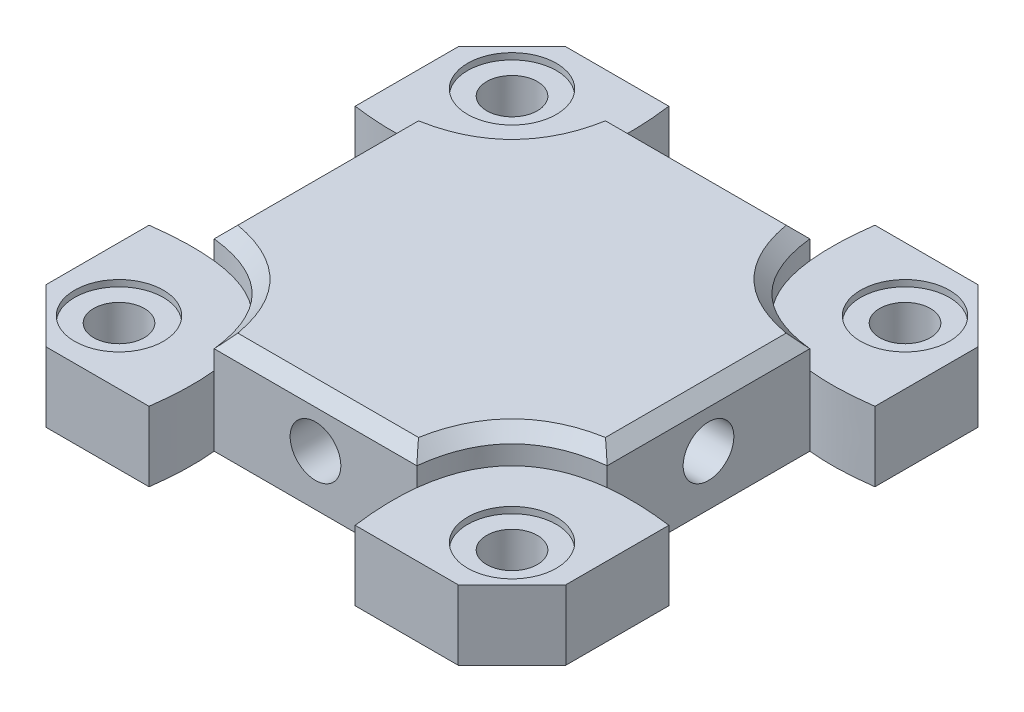
SolidWorks part; units mm, degrees
ref_plane "Front Plane" through (0, 0, 0) normal (0, 0, 1) x (1, 0, 0)
ref_plane "Top Plane" through (0, 0, 0) normal (0, 1, 0) x (1, 0, 0)
ref_plane "Right Plane" through (0, 0, 0) normal (1, 0, 0) x (0, 0, -1)
sketch "Sketch2" plane through (0, 0, 0) normal (0, 1, 0) x (1, 0, 0)
  line L1 (-20.5, -20.5) -> (20.5, -20.5)
  line L2 (-20.5, -20.5) -> (-20.5, 20.5)
  line L3 (-20.5, 20.5) -> (20.5, 20.5)
  line L4 (20.5, -20.5) -> (20.5, 20.5)
  line L5 (-20.5, -20.5) -> (20.5, 20.5) construction
  line L6 (-20.5, 20.5) -> (20.5, -20.5) construction
  point P0 (0, 0)
  dimension "D1" = 41
  dimension "D2" = 41
extrude "Boss-Extrude1" add sketch "Sketch2" along normal blind 2
sketch "Sketch3" plane through (0, 0, 0) normal (0, -1, 0) x (1, 0, 0)
  line L0 (-7.9432, -8.0372) -> (0, 0) construction
  line L5 (-7.9432, -8.0372) -> (7.9432, -8.0372) construction
  line L6 (-7.9432, -8.0372) -> (-7.9432, 8.0372) construction
  line L7 (-7.9432, 8.0372) -> (7.9432, 8.0372) construction
  line L8 (7.9432, -8.0372) -> (7.9432, 8.0372) construction
  line L9 (0, 0) -> (7.9432, 8.0372) construction
  line L10 (0, 0) -> (7.9432, -8.0372) construction
  line L11 (-7.9432, 8.0372) -> (0, 0) construction
  arc A1 (7.9432, 8.0372) -> (-7.9432, 8.0372) centre (0, 0) ccw construction
  arc A2 (-7.9432, -8.0372) -> (7.9432, -8.0372) centre (0, 0) ccw construction
  arc A3 (-7.9432, 8.0372) -> (-7.9432, -8.0372) centre (0, 0) ccw construction
  arc A4 (7.9432, -8.0372) -> (8.0686, 7.9112) centre (0, 0) ccw construction
  circle A5 centre (-7.9432, 8.0372) radius 2
  circle A10 centre (8.0372, 7.9432) radius 2
  circle A12 centre (7.9432, -8.0372) radius 2
  circle A13 centre (-8.0372, -7.9432) radius 2
  arc A14 (8.0686, 7.9112) -> (7.9432, 8.0372) centre (0, 0) ccw construction
  point P15 (-1.4144, -0.0142)
  point P19 (0, 0)
  dimension "D1" = 22.6
  dimension "D2" = 4
  dimension "D4" = 4
extrude "Cut-Extrude1" cut sketch "Sketch3" against normal through all
sketch "Sketch4" plane through (0, 2, 0) normal (0, 1, 0) x (1, 0, 0)
  circle A0 centre (0, 0) radius 7.5
  dimension "D1" = 15
extrude "Cut-Extrude2" cut sketch "Sketch4" against normal through all
sketch "Sketch5" plane through (0, 0, 0) normal (0, -1, 0) x (1, 0, 0)
  line L1 (-12.5, -12.5) -> (12.5, -12.5)
  line L2 (-12.5, -12.5) -> (-12.5, 12.5)
  line L3 (-12.5, 12.5) -> (12.5, 12.5)
  line L4 (12.5, -12.5) -> (12.5, 12.5)
  line L5 (-12.5, -12.5) -> (12.5, 12.5) construction
  line L6 (-12.5, 12.5) -> (12.5, -12.5) construction
  point P0 (0, 0)
  dimension "D1" = 25
  dimension "D2" = 25
extrude "Cut-Extrude3" cut sketch "Sketch5" against normal blind 1
sketch "Sketch6" plane through (0, 2, 0) normal (0, 1, 0) x (1, 0, 0)
  line L0 (-20.5, 16.2574) -> (-16.2574, 20.5)
  line L1 (-20.5, 20.5) -> (-20.5, -20.5) construction
  line L2 (20.5, 20.5) -> (-20.5, 20.5) construction
  line L4 (16.2574, 20.5) -> (20.5, 16.2574)
  line L5 (20.5, -20.5) -> (20.5, 20.5) construction
  line L7 (20.5, -16.2574) -> (16.2574, -20.5)
  line L8 (-20.5, -20.5) -> (20.5, -20.5) construction
  line L10 (-16.2574, -20.5) -> (-20.5, -16.2574)
  line L12 (-2.4898, 0) -> (5.6129, 0) construction
  line L13 (0, 5.0948) -> (0, 0) construction
  line L14 (0, 0) -> (3.8649, 3.8649) construction
  line L15 (-20.5, -16.2574) -> (-20.5, -20.5)
  line L16 (-20.5, -20.5) -> (-16.2574, -20.5)
  line L17 (16.2574, -20.5) -> (20.5, -20.5)
  line L18 (20.5, -20.5) -> (20.5, -16.2574)
  line L19 (20.5, 16.2574) -> (20.5, 20.5)
  line L20 (20.5, 20.5) -> (16.2574, 20.5)
  line L21 (-16.2574, 20.5) -> (-20.5, 20.5)
  line L22 (-20.5, 20.5) -> (-20.5, 16.2574)
  dimension "D1" = 6
  dimension "D2" = 6
  dimension "D3" = 45
  dimension "D4" = 6
  dimension "D5" = 6
extrude "Cut-Extrude4" cut sketch "Sketch6" against normal through all
sketch "Sketch7" plane through (0, 0, 0) normal (0, -1, 0) x (1, 0, 0)
  line L0 (-15.5, 15.5) -> (0, 0) construction
  line L1 (-15.5, -15.5) -> (15.5, -15.5) construction
  line L2 (-15.5, -15.5) -> (-15.5, 15.5) construction
  line L3 (-15.5, 15.5) -> (15.5, 15.5) construction
  line L4 (15.5, -15.5) -> (15.5, 15.5) construction
  line L5 (-15.5, -15.5) -> (0, 0) construction
  line L6 (0, 0) -> (15.5, -15.5) construction
  line L7 (0, 0) -> (15.5, 15.5) construction
  arc A0 (-15.5, -15.5) -> (15.5, -15.5) centre (0, 0) ccw construction
  arc A1 (-15.5, 15.5) -> (-15.5, -15.5) centre (0, 0) ccw construction
  arc A2 (15.5, -15.5) -> (15.5, 15.5) centre (0, 0) ccw construction
  arc A3 (15.5, 15.5) -> (-15.5, 15.5) centre (0, 0) ccw construction
  circle A4 centre (-15.5, 15.5) radius 2
  circle A5 centre (15.5, 15.5) radius 2
  circle A6 centre (15.5, -15.5) radius 2
  circle A7 centre (-15.5, -15.5) radius 2
  point P16 (0, 0)
  dimension "D2" = 4
  dimension "D4" = 31
  dimension "D3" = 4
extrude "Cut-Extrude5" cut sketch "Sketch7" against normal through all
sketch "Sketch8" plane through (0, 0, 0) normal (0, -1, 0) x (1, 0, 0)
  line L0 (-12.5, -12.5) -> (-12.5, 12.5) construction
  line L1 (-12.5, -12.5) -> (-20.477, -12.5) construction
  line L2 (-12.5, 12.5) -> (-20.477, 12.5) construction
  line L3 (-20.477, -12.5) -> (-20.477, 12.5) construction
  line L4 (12.5, -12.5) -> (12.5, 12.5) construction
  line L5 (12.5, -12.5) -> (20.4876, -12.5) construction
  line L6 (12.5, 12.5) -> (20.4876, 12.5) construction
  line L7 (20.4876, -12.5) -> (20.4876, 12.5) construction
  line L8 (-12.5, 12.5) -> (12.5, 12.5)
  line L9 (-12.5, 12.5) -> (-12.5, 20.5)
  line L10 (12.5, 12.5) -> (12.5, 20.5)
  line L11 (-12.5, 20.5) -> (12.5, 20.5)
  line L12 (12.5, -12.5) -> (-12.5, -12.5)
  line L13 (12.5, -12.5) -> (12.5, -20.4578)
  line L14 (-12.5, -12.5) -> (-12.5, -20.4578)
  line L15 (12.5, -20.4578) -> (-12.5, -20.4578)
  line L16 (-16.2574, 20.5) -> (16.2574, 20.5) construction
extrude "Boss-Extrude2" add sketch "Sketch8" along normal blind 3.5
sketch "Sketch9" plane through (0, -3.5, 0) normal (0, -1, 0) x (1, 0, 0)
  circle A0 centre (0, 16.5) radius 2
  circle A1 centre (0, -16.4789) radius 2
  dimension "D1" = 4
extrude "Cut-Extrude6" cut sketch "Sketch9" against normal through all
sketch "Sketch10" plane through (0, 0, 0) normal (0, -1, 0) x (1, 0, 0)
  line L0 (-20.5, -16.2574) -> (-16.2574, -20.5)
  line L1 (20.5, 12.5) -> (12.5, 12.5)
  line L2 (20.5, 12.5) -> (20.5, 16.2574)
  line L3 (16.2574, 20.5) -> (12.5, 20.5)
  line L4 (-20.5, 12.5) -> (-20.5, 16.2574)
  line L5 (-20.5, -12.5) -> (-12.5, -12.5)
  line L6 (-20.5, -12.5) -> (-20.5, -16.2574)
  line L8 (20.5, -12.5) -> (20.5, -16.2574)
  line L9 (-20.5, 16.2574) -> (-16.2574, 20.5)
  line L10 (16.2574, 20.5) -> (20.5, 16.2574)
  line L11 (20.5, -16.2574) -> (16.2574, -20.5)
  line L12 (-20.5, -12.5) -> (-20.5, -16.2574)
  line L13 (-12.5, 12.5) -> (-20.5, 12.5)
  line L14 (-12.5, 20.5) -> (-16.2574, 20.5)
  line L15 (12.5, -12.5) -> (20.5, -12.5)
  line L16 (-12.5, -12.5) -> (-12.5, 12.5)
  line L17 (-12.5, 12.5) -> (-12.5, 20.5)
  line L18 (-12.5, 20.5) -> (-16.2574, 20.5)
  line L19 (-16.2574, 20.5) -> (-20.5, 16.2574)
  line L20 (-20.5, 16.2574) -> (-20.5, -16.2574)
  line L21 (-20.5, -16.2574) -> (-16.2574, -20.5)
  line L22 (-16.2574, -20.5) -> (16.2574, -20.5)
  line L23 (16.2574, -20.5) -> (20.5, -16.2574)
  line L24 (20.5, -16.2574) -> (20.5, 16.2574)
  line L25 (20.5, 16.2574) -> (16.2574, 20.5)
  line L26 (16.2574, 20.5) -> (12.5, 20.5)
  line L27 (12.5, 20.5) -> (12.5, 12.5)
  line L28 (12.5, 12.5) -> (12.5, -12.5)
  line L29 (12.5, -12.5) -> (12.5, -20.4578)
  line L30 (12.5, -20.4578) -> (-12.5, -20.4578)
  line L31 (-12.5, -20.4578) -> (-12.5, -12.5)
  line L33 (-12.5, 12.5) -> (-12.5, 20.5)
  line L34 (-12.5, 20.5) -> (-16.2574, 20.5)
  line L35 (-16.2574, 20.5) -> (-20.5, 16.2574)
  line L36 (-20.5, 16.2574) -> (-20.5, 12.5)
  line L37 (-20.5, -16.2574) -> (-16.2574, -20.5)
  line L39 (16.2574, -20.5) -> (20.5, -16.2574)
  line L40 (20.5, -16.2574) -> (20.5, 16.2574)
  line L41 (20.5, 16.2574) -> (16.2574, 20.5)
  line L42 (16.2574, 20.5) -> (12.5, 20.5)
  line L43 (12.5, 20.5) -> (12.5, 12.5)
  line L44 (12.5, 12.5) -> (12.5, -12.5)
  line L45 (12.5, -12.5) -> (12.5, -20.4578)
  line L47 (-12.5, -20.4578) -> (-12.5, -12.5)
  line L50 (12.5, 20.5) -> (-12.5, 20.5) construction
  circle A0 centre (-15.5, 15.5) radius 2
  circle A1 centre (15.5, 15.5) radius 2
  circle A2 centre (15.5, -15.5) radius 2
  circle A3 centre (-15.5, -15.5) radius 2
  circle M19 centre (-15.5, -15.5) radius 2
  circle M20 centre (15.5, -15.5) radius 2
  circle M21 centre (15.5, 15.5) radius 2
  circle M22 centre (-15.5, 15.5) radius 2
  line M24 (-12.5, 12.5) -> (-12.5, 20.5)
  line M25 (-12.5, 20.5) -> (-16.2574, 20.5)
  line M26 (-16.2574, 20.5) -> (-20.5, 16.2574)
  line M27 (-20.5, 16.2574) -> (-20.5, -16.2574)
  line M28 (-20.5, -16.2574) -> (-16.2574, -20.5)
  line M29 (-16.2574, -20.5) -> (16.2574, -20.5)
  line M30 (16.2574, -20.5) -> (20.5, -16.2574)
  line M31 (20.5, -16.2574) -> (20.5, 16.2574)
  line M32 (20.5, 16.2574) -> (16.2574, 20.5)
  line M33 (16.2574, 20.5) -> (12.5, 20.5)
  line M34 (12.5, 20.5) -> (12.5, 12.5)
  line M36 (12.5, -12.5) -> (12.5, -20.4578)
  line M37 (12.5, -20.4578) -> (-12.5, -20.4578)
  line M38 (-12.5, -20.4578) -> (-12.5, -12.5)
  dimension "D1" = 0
extrude "Boss-Extrude3" add sketch "Sketch10" along normal up to surface (3.5 mm away) contours L13 M24 M25 M26 M27 M22 | L1 M31 M32 M33 M34 M21 | L15 L5 M36 M37 M38 M27 M28 M29 M30 M31 M19 M20 region at (-20.0823, 0, -14.3787) region at (-20.3869, 0, 14.3787) region at (16.5, 0, 12.6131) up to face at (0, -3.5, 14.5)
sketch "Sketch11" plane through (0, 2, 0) normal (0, 1, 0) x (1, 0, 0)
  circle A0 centre (-15.5, 15.5) radius 3.5
  circle A1 centre (15.5, 15.5) radius 3.5
  circle A2 centre (15.5, -15.5) radius 3.5
  circle A3 centre (-15.5, -15.5) radius 3.5
  point P12 (0, 0)
  dimension "D1" = 7
  dimension "D2" = 4
extrude "Cut-Extrude7" cut sketch "Sketch11" against normal offset from surface (3.5 mm away) 2 up to face at (0, -3.5, -18.4789)
sketch "Sketch12" plane through (0, 0, 0) normal (0, -1, 0) x (1, 0, 0)
  line L0 (-12.5, 12.5) -> (-12.5, -12.5) construction
  line L1 (-20.5, -12.5) -> (-12.5, -12.5)
  line L2 (-20.5, -12.5) -> (-20.5, -10.5)
  line L3 (-20.5, -10.5) -> (-12.5, -10.5)
  line L4 (-12.5, -12.5) -> (-12.5, -10.5)
  line L5 (-25.9518, 0) -> (26.3784, 0) construction
  line L6 (0, 23.4974) -> (0, -23.7021) construction
  line L7 (-12.5, 12.5) -> (-12.5, 10.5)
  line L8 (-20.5, 12.5) -> (-12.5, 12.5)
  line L9 (-20.5, 12.5) -> (-20.5, 10.5)
  line L10 (-20.5, 10.5) -> (-12.5, 10.5)
  line L11 (12.5, -12.5) -> (12.5, -10.5)
  line L12 (20.5, -10.5) -> (12.5, -10.5)
  line L13 (20.5, -12.5) -> (20.5, -10.5)
  line L14 (20.5, -12.5) -> (12.5, -12.5)
  line L15 (20.5, 10.5) -> (12.5, 10.5)
  line L16 (20.5, 12.5) -> (20.5, 10.5)
  line L17 (20.5, 12.5) -> (12.5, 12.5)
  line L18 (12.5, 12.5) -> (12.5, 10.5)
  dimension "D1" = 2
extrude "Boss-Extrude4" add sketch "Sketch12" along normal up to surface (3.5 mm away) up to face at (0, -3.5, 14.5)
sketch "Sketch13" plane through (0, 2, 0) normal (0, 1, 0) x (1, 0, 0)
  circle A0 centre (-15.5, 15.5) radius 3.5
  circle A1 centre (15.5, 15.5) radius 3.5
  circle A2 centre (15.5, -15.5) radius 3.5
  circle A3 centre (-15.5, -15.5) radius 3.5
  point P12 (0, 0)
  dimension "D1" = 4
extrude "Cut-Extrude8" cut sketch "Sketch13" against normal up to surface (3.5 mm away) up to face at (-15.5, -1.5, -13.5)
sketch "Sketch14" plane through (0, -1.5, 0) normal (0, 1, 0) x (1, 0, 0)
  circle A0 centre (-15.5, -15.5) radius 2
  circle A1 centre (-15.5, -15.5) radius 3.5
  circle A2 centre (-15.5, 15.5) radius 3.5
  circle A3 centre (-15.5, 15.5) radius 2
  circle A4 centre (15.5, 15.5) radius 3.5
  circle A5 centre (15.5, 15.5) radius 2
  circle A6 centre (15.5, -15.5) radius 3.5
  circle A7 centre (15.5, -15.5) radius 2
  point P16 (0, 0)
  dimension "D1" = 4
extrude "Boss-Extrude5" add sketch "Sketch14" along normal offset from surface (3 mm away) 0.5 up to face at (-15.5, 2, 19)
sketch "Sketch15" plane through (0, 2, 0) normal (0, 1, 0) x (1, 0, 0)
  line L0 (0, 20.5) -> (0, -20.5) construction
  line L1 (16.2574, 20.5) -> (-16.2574, 20.5) construction
  line L2 (-16.2574, -20.5) -> (16.2574, -20.5) construction
  line L3 (0, -16.5) -> (8, -16.5) construction
  line L4 (0, -16.5) -> (-8, -16.5) construction
  line L5 (0, 16.4789) -> (8, 16.4789) construction
  line L6 (0, 16.4789) -> (-8, 16.4789) construction
  line L7 (-8, 20.5) -> (-8, 16.4789) construction
  line L8 (-8, 16.4789) -> (-8, 12.4578) construction
  line L9 (-8, -20.5) -> (-8, -16.5) construction
  line L10 (-8, -16.5) -> (-8, -12.5) construction
  line L11 (-3.025, 0) -> (3.025, 0) construction
  line L12 (8, 12.4578) -> (-8, 12.4578)
  line L13 (8, 12.4578) -> (8, 20.5)
  line L14 (8, 20.5) -> (-8, 20.5)
  line L15 (-8, 12.4578) -> (-8, 20.5)
  line L16 (8, -12.5) -> (-8, -12.5)
  line L17 (8, -12.5) -> (8, -20.5)
  line L18 (8, -20.5) -> (-8, -20.5)
  line L19 (-8, -12.5) -> (-8, -20.5)
  circle A0 centre (0, 16.4789) radius 2
  circle A1 centre (0, -16.4789) radius 2
  dimension "D1" = 8
extrude "Boss-Extrude6" add sketch "Sketch15" along normal blind 4
chamfer "Chamfer1" distance 0.5 angle 45 2 edges at (0, 6, 14.4789) (0, 6, -14.4789)
chamfer "Chamfer2" distance 0.5 angle 45 8 edges at (8, 6, 16.5) (0, 6, 20.5) (-8, 6, 16.5) (0, 6, 12.5) (-8, 6, -16.4789) (0, 6, -20.5) (8, 6, -16.4789) (0, 6, -12.4578)
sketch "Sketch16" plane through (0, -3.5, 0) normal (0, -1, 0) x (1, 0, 0)
  line L0 (-20.5, 10.5) -> (-20.5, 16.2574) construction
  line L1 (-12.5, -12.5) -> (-20.5, -12.5)
  line L2 (-12.5, -12.5) -> (-12.5, 12.5)
  line L3 (-12.5, 12.5) -> (-20.5, 12.5)
  line L4 (-20.5, -12.5) -> (-20.5, 12.5)
  line L5 (12.5, 12.5) -> (20.5, 12.5)
  line L6 (12.5, 12.5) -> (12.5, -12.5)
  line L7 (20.5, 12.5) -> (20.5, -12.5)
  line L8 (12.5, -12.5) -> (20.5, -12.5)
  line L9 (20.5, 16.2574) -> (20.5, 10.5) construction
extrude "Cut-Extrude9" cut sketch "Sketch16" against normal up to surface (3.5 mm away) up to face at (16.5, 0, 0)
sketch "Sketch17" plane through (0, 6, 0) normal (0, 1, 0) x (1, 0, 0)
  line L1 (15.3001, -24.9451) -> (-15.3001, -24.9451)
  line L2 (15.3001, -24.9451) -> (15.3001, 24.9451)
  line L3 (15.3001, 24.9451) -> (-15.3001, 24.9451)
  line L4 (-15.3001, -24.9451) -> (-15.3001, 24.9451)
  line L5 (15.3001, -24.9451) -> (-15.3001, 24.9451) construction
  line L6 (15.3001, 24.9451) -> (-15.3001, -24.9451) construction
  point P0 (0, 0)
extrude "Cut-Extrude10" cut sketch "Sketch17" against normal up to surface (4 mm away) up to face at (0, 2, 0.0053)
sketch "Sketch18" plane through (0, 2, 0) normal (0, 1, 0) x (1, 0, 0)
  circle A0 centre (0, 0) radius 14.015
extrude "Boss-Extrude7" add sketch "Sketch18" against normal up to surface (1 mm away) up to face at (8.0372, 1, 9.9432)
sketch "Sketch19" plane through (0, 2, 0) normal (0, 1, 0) x (1, 0, 0)
  circle A0 centre (0, 16.4789) radius 2
  circle A1 centre (0, -16.5) radius 2
extrude "Boss-Extrude8" add sketch "Sketch19" against normal up to surface (5.5 mm away) up to face at (0, -3.5, -18.4789)
sketch "Sketch20" plane through (0, 2, 0) normal (0, 1, 0) x (1, 0, 0)
  line L0 (0, 0) -> (-10, 0) construction
  circle A0 centre (-10, 0) radius 2
  circle A1 centre (0, 10) radius 2
  circle A2 centre (10, 0) radius 2
  circle A3 centre (0, -10) radius 2
  point P13 (0, 0)
  dimension "D2" = 4
  dimension "D1" = 10
  dimension "D3" = 4
sketch "Sketch21" plane through (0, 1, 0) normal (0, -1, 0) x (1, 0, 0)
  line L0 (-20.5, -16.2574) -> (-20.5, -12.5) construction
  line L1 (20.5, 12.5) -> (-20.5, 12.5)
  line L2 (20.5, 12.5) -> (20.5, -12.5)
  line L3 (20.5, -12.5) -> (-20.5, -12.5)
  line L4 (-20.5, 12.5) -> (-20.5, -12.5)
  line L5 (20.5, 12.5) -> (-20.5, -12.5) construction
  line L6 (20.5, -12.5) -> (-20.5, 12.5) construction
  line L7 (20.5, -12.5) -> (-20.5, -12.5) construction
  point P0 (0, 0)
extrude "Boss-Extrude9" add sketch "Sketch21" along normal up to surface (4.5 mm away) up to face at (0, -3.5, -16.4191)
sketch "Sketch22" plane through (0, 2, 0) normal (0, 1, 0) x (1, 0, 0)
  line L0 (0, 20.5) -> (0, 0) construction
  line L1 (16.2574, 20.5) -> (-16.2574, 20.5) construction
  line L2 (0, 0) -> (-20.5, 0) construction
  line L3 (-20.5, 16.2574) -> (-20.5, -16.2574) construction
  line L4 (0, 0) -> (0, -20.5) construction
  line L5 (-16.2574, -20.5) -> (16.2574, -20.5) construction
  line L6 (0, 0) -> (20.5, 0) construction
  line L7 (20.5, -16.2574) -> (20.5, 16.2574) construction
  line L8 (-20.5, 0) -> (-20.5, 16.2574) construction
  line L9 (0, 20.5) -> (-16.2574, 20.5) construction
  line L10 (-20.5, 0) -> (-20.5, -16.2574) construction
  line L11 (0, -20.5) -> (-16.2574, -20.5) construction
  line L12 (-8.1287, -20.5) -> (-20.5, -8.1287) construction
  line L13 (-8.1287, 20.5) -> (-20.5, 8.1287) construction
  line L14 (0, -20.5) -> (16.2574, -20.5) construction
  line L15 (20.5, 0) -> (20.5, -16.2574) construction
  line L16 (8.1287, -20.5) -> (20.5, -8.1287) construction
  line L17 (0, 20.5) -> (16.2574, 20.5) construction
  line L18 (20.5, 16.2574) -> (20.5, 0) construction
  line L19 (20.5, 8.1287) -> (8.1287, 20.5) construction
  line L20 (-14.3143, 14.3143) -> (-10.25, 10.25) construction
  line L21 (-10.25, -10.25) -> (-14.3143, -14.3143) construction
  line L22 (-20.5, 0) -> (0, 20.5) construction
  line L23 (0, 20.5) -> (20.5, 0) construction
  line L24 (20.5, 0) -> (0, -20.5) construction
  line L25 (0, -20.5) -> (-20.5, 0) construction
  line L26 (10.25, 10.25) -> (14.3143, 14.3143) construction
  line L27 (10.25, -10.25) -> (14.3143, -14.3143) construction
  line L28 (-20.5, 8.1287) -> (-20.5, -8.1287)
  line L29 (-8.1287, -20.5) -> (8.1287, -20.5)
  line L30 (20.5, -8.1287) -> (20.5, 8.1287)
  line L31 (-8.1287, 20.5) -> (8.1287, 20.5)
  spline S0 degree 2 poles (-8.1287, 20.5) (-6.1857, 6.1857) (-20.5, 8.1287) knots 0 0 0 1 1 1
  spline S1 degree 2 poles (8.1287, -20.5) (6.1857, -6.1857) (20.5, -8.1287) knots 0 0 0 1 1 1
  spline S2 degree 2 poles (-20.5, -8.1287) (-6.1857, -6.1857) (-8.1287, -20.5) knots 0 0 0 1 1 1
  spline S3 degree 2 poles (8.1287, 20.5) (6.1857, 6.1857) (20.5, 8.1287) knots 0 0 0 1 1 1
extrude "Boss-Extrude10" add sketch "Sketch22" along normal blind 2.5
sketch "Sketch24" plane through (0, 4.5, 0) normal (0, 1, 0) x (1, 0, 0)
  line L0 (-7.9931, 15.5) -> (7.9931, 15.5) construction
  line L1 (15.5, 7.9931) -> (15.5, -7.9931) construction
  line L2 (7.9931, -15.5) -> (-7.9931, -15.5) construction
  line L3 (-15.5, -7.9931) -> (-15.5, 7.9931) construction
  line L4 (-20.5, 8.1287) -> (-20.5, -8.1287)
  line L5 (-8.1287, -20.5) -> (8.1287, -20.5)
  line L6 (20.5, -8.1287) -> (20.5, 8.1287)
  line L7 (8.1287, 20.5) -> (-8.1287, 20.5)
  line L8 (-20.5, 8.1287) -> (-20.5, -8.1287)
  line L9 (-8.1287, -20.5) -> (8.1287, -20.5)
  line L10 (20.5, -8.1287) -> (20.5, 8.1287)
  line L11 (8.1287, 20.5) -> (-8.1287, 20.5)
  line L12 (-7.9931, 15.5) -> (7.9931, 15.5)
  line L13 (15.5, 7.9931) -> (15.5, -7.9931)
  line L14 (7.9931, -15.5) -> (-7.9931, -15.5)
  line L15 (-15.5, -7.9931) -> (-15.5, 7.9931)
  parabola Q0 (-7.9931, -15.5) -> (-8.1287, -20.5) focus (-12.6035, -12.6035) apex (-10.25, -10.25)
  parabola Q1 (-15.5, 7.9931) -> (-20.5, 8.1287) focus (-12.6035, 12.6035) apex (-10.25, 10.25)
  parabola Q2 (7.9931, 15.5) -> (8.1287, 20.5) focus (12.6035, 12.6035) apex (10.25, 10.25)
  parabola Q3 (15.5, -7.9931) -> (20.5, -8.1287) focus (12.6035, -12.6035) apex (10.25, -10.25)
  parabola Q4 (-8.1287, 20.5) -> (-20.5, 8.1287) focus (-12.6035, 12.6035) apex (-10.25, 10.25)
  parabola Q5 (-20.5, -8.1287) -> (-8.1287, -20.5) focus (-12.6035, -12.6035) apex (-10.25, -10.25)
  parabola Q6 (8.1287, -20.5) -> (20.5, -8.1287) focus (12.6035, -12.6035) apex (10.25, -10.25)
  parabola Q7 (20.5, 8.1287) -> (8.1287, 20.5) focus (12.6035, 12.6035) apex (10.25, 10.25)
  parabola Q8 (-8.1287, 20.5) -> (-7.9931, 15.5) focus (-12.6035, 12.6035) apex (-10.25, 10.25)
  parabola Q9 (-20.5, -8.1287) -> (-15.5, -7.9931) focus (-12.6035, -12.6035) apex (-10.25, -10.25)
  parabola Q10 (8.1287, -20.5) -> (7.9931, -15.5) focus (12.6035, -12.6035) apex (10.25, -10.25)
  parabola Q11 (20.5, 8.1287) -> (15.5, 7.9931) focus (12.6035, 12.6035) apex (10.25, 10.25)
  dimension "D1" = 0
extrude "Cut-Extrude12" cut sketch "Sketch24" against normal through all
sketch "Sketch25" plane through (0, 0, 15.5) normal (0, 0, 1) x (1, 0, 0)
  line L0 (-7.9931, 4.5) -> (7.9931, -3.5) construction
  line L1 (-7.9931, -3.5) -> (7.9931, 4.5) construction
  line L2 (7.9931, 2) -> (7.9931, 4.5) construction
  circle A0 centre (0, 0.5) radius 2
  dimension "D1" = 4
extrude "Cut-Extrude13" cut sketch "Sketch25" against normal blind 5
mirror "Mirror1" about plane through (0, 0, 0) normal (0, 0, 1) of "Cut-Extrude13"
sketch "Sketch26" plane through (15.5, 0, 0) normal (1, 0, 0) x (0, 0, -1)
  line L0 (7.9931, -3.5) -> (-7.9931, 4.5) construction
  line L1 (-7.9931, -3.5) -> (7.9931, 4.5) construction
  circle A0 centre (0, 0.5) radius 2
  dimension "D1" = 4
extrude "Cut-Extrude14" cut sketch "Sketch26" against normal blind 5
mirror "Mirror2" about plane through (0, 0, 0) normal (1, 0, 0) of "Cut-Extrude14"
chamfer "Chamfer3" distance 1 angle 45 8 edges
